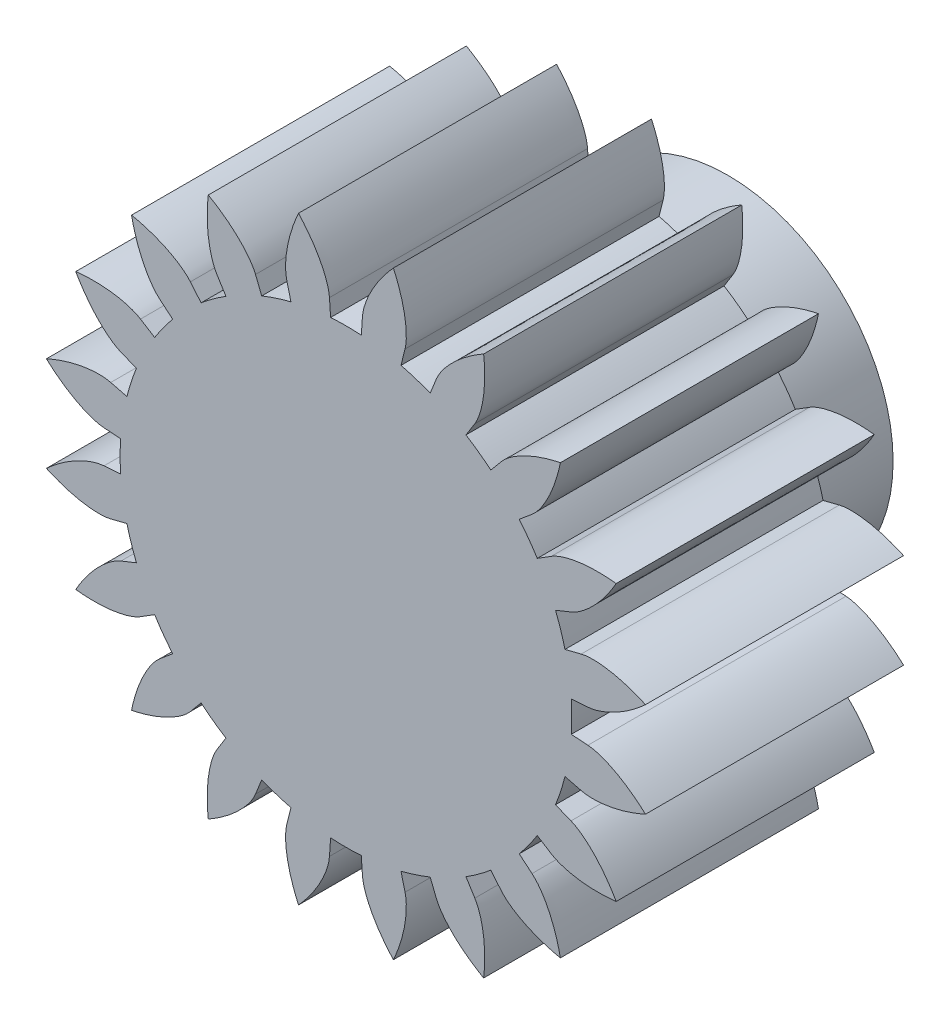
SolidWorks part; units mm, degrees
ref_plane "前视基准面" through (0, 0, 0) normal (0, 0, 1) x (1, 0, 0)
ref_plane "上视基准面" through (0, 0, 0) normal (0, 1, 0) x (1, 0, 0)
ref_plane "右视基准面" through (0, 0, 0) normal (1, 0, 0) x (0, 0, -1)
other "Configuration Table"
sketch "草图1" plane through (0, 0, 0) normal (0, 0, 1) x (1, 0, 0)
  line L0 (0, 0) -> (5, 0) construction
  line L1 (0, 0) -> (4.9846, 0.3923) construction
  line L2 (0, 0) -> (4.6876, 0.3194)
  line L3 (4.9846, 0.3923) -> (4.9846, -0.3923) construction
  line L4 (0, 0) -> (4.6876, -0.3194)
  circle A0 centre (0, 0) radius 5.5
  circle A1 centre (0, 0) radius 5 construction
  circle A2 centre (0, 0) radius 4.375
  circle A3 centre (0, 0) radius 4.6985 construction
  circle A4 centre (0, 0) radius 1.475
  circle A5 centre (0, 0) radius 6.5
  spline S0 degree 4 poles (4.6876, 0.3194) (4.7233, 0.3218) (4.8225, 0.336) (5.0062, 0.3926) (5.2885, 0.5242) (5.6241, 0.7499) (6.0094, 1.0976) (6.395, 1.5688) (6.7398, 2.1414) (7.0933, 2.9696) (7.3065, 3.8467) (7.3947, 4.7795) (7.347, 5.8934) (7.1568, 6.9938) (6.7515, 8.227) (6.0949, 9.5107) (5.2611, 10.6861) (4.2765, 11.7378) (3.1662, 12.6551) (1.9531, 13.4307) (0.6586, 14.0604) (-0.5283, 14.4821) (-1.4854, 14.7287) (-2.1912, 14.8654) (-2.6338, 14.9356) (-2.9917, 14.9827) (-3.3451, 15.0208) (-3.7095, 15.05) (-4.0266, 15.0684) (-4.3306, 15.0786) (-4.6986, 15.0842) (-4.9527, 15.0816) (-5.4001, 15.0704) (-5.6957, 15.0494) (-6.0237, 15.027) (-6.2862, 14.9991) (-6.5922, 14.9657) (-6.7961, 14.9366) (-6.9439, 14.9154) (-7.0152, 14.9043) knots 0 0 0 0 0 0.005604 0.015718 0.02996 0.048734 0.068727 0.096889 0.125051 0.153212 0.209535 0.237696 0.271429 0.327752 0.384075 0.440398 0.496721 0.553044 0.609367 0.66569 0.722013 0.778336 0.806497 0.820578 0.834659 0.84874 0.86282 0.876901 0.890982 0.900036 0.909091 0.931818 0.943182 0.954545 0.965909 0.977273 0.988636 1 1 1 1 1 construction
  spline S1 degree 4 poles (4.6876, 0.3194) (4.7233, 0.3218) (4.8225, 0.336) (5.0062, 0.3926) (5.2885, 0.5242) (5.6241, 0.7499) (6.0094, 1.0976) (6.395, 1.5688) (6.7398, 2.1414) (7.0933, 2.9696) (7.3065, 3.8467) (7.3947, 4.7795) (7.347, 5.8934) (7.1568, 6.9938) (6.7515, 8.227) (6.0949, 9.5107) (5.2611, 10.6861) (4.2765, 11.7378) (3.1662, 12.6551) (1.9531, 13.4307) (0.6586, 14.0604) (-0.5283, 14.4821) (-1.4854, 14.7287) (-2.1912, 14.8654) (-2.6338, 14.9356) (-2.9917, 14.9827) (-3.3451, 15.0208) (-3.7095, 15.05) (-4.0266, 15.0684) (-4.3306, 15.0786) (-4.5463, 15.0819) (-4.6529, 15.0825) (-4.7054, 15.0825) knots 0 0 0 0 0 0.005604 0.015718 0.02996 0.048734 0.068727 0.096889 0.125051 0.153212 0.209535 0.237696 0.271429 0.327752 0.384075 0.440398 0.496721 0.553044 0.609367 0.66569 0.722013 0.778336 0.806497 0.820578 0.834659 0.84874 0.86282 0.876901 0.890982 0.900036 0.909091 0.909091 0.909091 0.909091 0.909091
  spline S2 degree 4 poles (4.6876, -0.3194) (4.7233, -0.3218) (4.8225, -0.336) (5.0062, -0.3926) (5.2885, -0.5242) (5.6241, -0.7499) (6.0094, -1.0976) (6.395, -1.5688) (6.7398, -2.1414) (7.0933, -2.9696) (7.3065, -3.8467) (7.3947, -4.7795) (7.347, -5.8934) (7.1568, -6.9938) (6.7515, -8.227) (6.0949, -9.5107) (5.2611, -10.6861) (4.2765, -11.7378) (3.1662, -12.6551) (1.9531, -13.4307) (0.6586, -14.0604) (-0.5283, -14.4821) (-1.4854, -14.7287) (-2.1912, -14.8654) (-2.6338, -14.9356) (-2.9917, -14.9827) (-3.3451, -15.0208) (-3.7095, -15.05) (-4.0266, -15.0684) (-4.3306, -15.0786) (-4.6986, -15.0842) (-4.9527, -15.0816) (-5.4001, -15.0704) (-5.6957, -15.0494) (-6.0237, -15.027) (-6.2862, -14.9991) (-6.5922, -14.9657) (-6.7961, -14.9366) (-6.9439, -14.9154) (-7.0152, -14.9043) knots 0 0 0 0 0 0.005604 0.015718 0.02996 0.048734 0.068727 0.096889 0.125051 0.153212 0.209535 0.237696 0.271429 0.327752 0.384075 0.440398 0.496721 0.553044 0.609367 0.66569 0.722013 0.778336 0.806497 0.820578 0.834659 0.84874 0.86282 0.876901 0.890982 0.900036 0.909091 0.931818 0.943182 0.954545 0.965909 0.977273 0.988636 1 1 1 1 1 construction
  spline S3 degree 4 poles (4.6876, -0.3194) (4.7233, -0.3218) (4.8225, -0.336) (5.0062, -0.3926) (5.2885, -0.5242) (5.6241, -0.7499) (6.0094, -1.0976) (6.395, -1.5688) (6.7398, -2.1414) (7.0933, -2.9696) (7.3065, -3.8467) (7.3947, -4.7795) (7.347, -5.8934) (7.1568, -6.9938) (6.7515, -8.227) (6.0949, -9.5107) (5.2611, -10.6861) (4.2765, -11.7378) (3.1662, -12.6551) (1.9531, -13.4307) (0.6586, -14.0604) (-0.5283, -14.4821) (-1.4854, -14.7287) (-2.1912, -14.8654) (-2.6338, -14.9356) (-2.9917, -14.9827) (-3.3451, -15.0208) (-3.7095, -15.05) (-4.0266, -15.0684) (-4.3306, -15.0786) (-4.5463, -15.0819) (-4.6529, -15.0825) (-4.7054, -15.0825) knots 0 0 0 0 0 0.005604 0.015718 0.02996 0.048734 0.068727 0.096889 0.125051 0.153212 0.209535 0.237696 0.271429 0.327752 0.384075 0.440398 0.496721 0.553044 0.609367 0.66569 0.722013 0.778336 0.806497 0.820578 0.834659 0.84874 0.86282 0.876901 0.890982 0.900036 0.909091 0.909091 0.909091 0.909091 0.909091
  point P15 (4.9846, 0)
  dimension "齿顶圆直径" = 11
  dimension "分度圆直径" = 10
  dimension "齿根圆直径" = 8.75
  dimension "基圆直径" = 9.3969
  dimension "内孔直径" = 2.95
  dimension "渐近线镜像线夹角" = 4.5
  dimension "D1" = 1
extrude "凸台-拉伸1" add sketch "草图1" along normal blind 5 contours A0 | A4
sketch "草图6" plane through (0, 0, 5) normal (0, 0, 1) x (1, 0, 0)
  circle A0 centre (0, 0) radius 6
  circle A1 centre (0, 0) radius 5.5 construction
  circle M1 centre (0, 0) radius 5.5
  dimension "D1" = 0.5
extrude "凸台-拉伸4" add sketch "草图6" against normal up to surface (5 mm away) contours A0 M1 region at (-5.8303, 0, 5) up to face at (5.5, 0, 0)
extrude "切除-拉伸1" cut sketch "草图1<3>" along normal through all contours A2 S3 A0 S1 | A0 S3 A5 S1 region at (5.0102, 0, 0) region at (6.0346, 0, 0)
sketch "草图1<3>" plane through (0, 0, 0) normal (0, 0, 1) x (1, 0, 0) same geometry as "草图1"
pattern_circular "阵列(圆周)1" count 20 every 18 about axis through (0, 0, 5) along (0, 0, -1) of "切除-拉伸1" reverse direction yes
sketch "草图2" plane through (0, 0, 5) normal (0, 0, 1) x (1, 0, 0)
  circle A0 centre (0, 0) radius 1.475
extrude "凸台-拉伸2" add sketch "草图2" against normal through all
sketch "草图3" plane through (0, 0, 0) normal (0, 0, -1) x (-1, 0, 0)
  line L1 (0.6, 1.0392) -> (-0.6, 1.0392)
  line L2 (-0.6, 1.0392) -> (-1.2, 0)
  line L3 (-1.2, 0) -> (-0.6, -1.0392)
  line L4 (-0.6, -1.0392) -> (0.6, -1.0392)
  line L5 (0.6, -1.0392) -> (1.2, 0)
  line L6 (1.2, 0) -> (0.6, 1.0392)
  circle A0 centre (0, 0) radius 2.2
  circle A1 centre (0, 0) radius 3.2
  circle A2 centre (0, 0) radius 1.0392 construction
  dimension "D1" = 1
  dimension "D2" = 4.4
  dimension "D3" = 1.2
extrude "凸台-拉伸3" add sketch "草图3" along normal blind 2.4 contours A1 A0 | L5 L6 L1 L2 L3 L4 region at (0, 0, 0) region at (3.1095, 0, 0)
sketch "草图4" plane through (0, 0, 5) normal (0, 0, 1) x (1, 0, 0)
  line L0 (1, 1.118) -> (1, -1.118)
  circle A0 centre (0, 0) radius 1.5
  dimension "D1" = 3
  dimension "D2" = 1
sketch "草图5" plane through (0, 0, -2.4) normal (0, 0, -1) x (-1, 0, 0)
  circle A0 centre (0, 0) radius 1.2
extrude "切除-拉伸2" cut sketch "草图5" against normal blind 1
equation "\"m\"= 0.5'模数"
equation "\"z\"= 20'齿数"
equation "\"a\"= 20度'压力角"
equation "\"d\"= \"m\" * \"z\"'分度圆直径"
equation "\"da\"= ( \"z\" + 2 ) * \"m\"'齿顶圆直径"
equation "\"df\"= ( \"z\" - 2.5 ) * \"m\"'齿根圆直径"
equation "\"s\"= 0.5 * PI * \"m\"'分度圆齿厚"
equation "\"r\"= 0.38 * \"m\"'齿根圆角"
equation "\"B\"= 0.3 * \"d\"'齿厚"
equation "\"db\"= \"m\" * \"z\" * cos ( \"a\" )'基圆直径"
equation "\"rb\"= \"db\" / 2'基圆半径"
equation "\"齿顶圆直径@草图1\"= \"da\""
equation "\"分度圆直径@草图1\"= \"d\""
equation "\"齿根圆直径@草图1\"= \"df\""
equation "\"基圆直径@草图1\"= \"db\""
equation "\"渐近线镜像线夹角@草图1\"= 360 / 4 / \"z\""
equation "\"h\"= 5'齿轮厚度"
equation "\"ir\"= 2.95'内孔直径"
equation "\"内孔直径@草图1\"= \"ir\""
equation "\"齿轮厚@凸台-拉伸1\"= \"h\""
equation "\"齿轮夹角@阵列(圆周)1\"= 360 / \"z\""
equation "\"齿数@阵列(圆周)1\"= \"z\""
